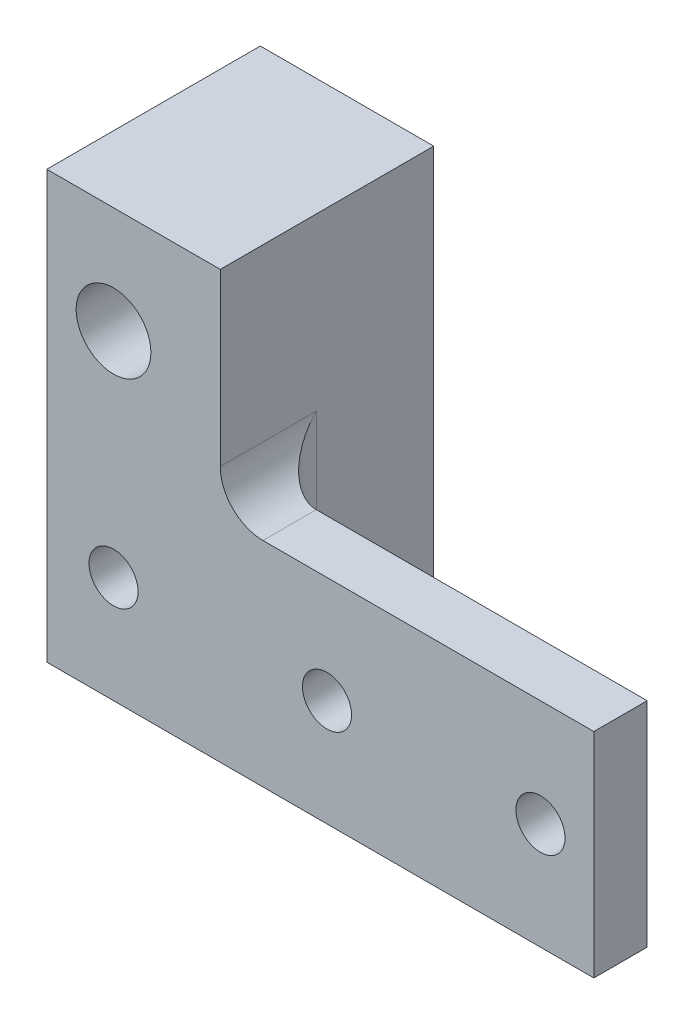
SolidWorks part; units mm, degrees
ref_plane "Front Plane" through (0, 0, 0) normal (0, 0, 1) x (1, 0, 0)
ref_plane "Top Plane" through (0, 0, 0) normal (0, 1, 0) x (1, 0, 0)
ref_plane "Right Plane" through (0, 0, 0) normal (1, 0, 0) x (0, 0, -1)
sketch "Sketch1" plane through (0, 0, 0) normal (0, 0, 1) x (1, 0, 0)
  line L0 (0, 0) -> (0, 50.8)
  line L1 (0, 50.8) -> (25.4, 50.8)
  line L2 (25.4, 50.8) -> (25.4, 25.4)
  line L3 (25.4, 25.4) -> (69.85, 25.4)
  line L4 (69.85, 25.4) -> (69.85, 0)
  line L5 (69.85, 0) -> (0, 0)
  dimension "D1" = 50.8
  dimension "D2" = 25.4
  dimension "2.75" = 69.85
extrude "Boss-Extrude1" add sketch "Sketch1" along normal blind 25.4
sketch "Sketch2" plane through (0, 0, 25.4) normal (0, 0, 1) x (1, 0, 0)
  line L0 (25.4, 50.8) -> (0, 50.8) construction
  line L1 (25.4, 25.4) -> (25.4, 50.8) construction
  line L2 (0, 0) -> (69.85, 0) construction
  circle A0 centre (12.7, 38.1) radius 2.921
  circle A1 centre (12.7, 12.7) radius 2.921
  circle A2 centre (38.1, 12.7) radius 2.921
  circle A3 centre (63.5, 12.7) radius 2.921
  dimension "D1" = 5.842
  dimension "D2" = 12.7
  dimension "D3" = 12.7
  dimension "D4" = 12.7
  dimension "D5" = 3
extrude "Cut-Extrude1" cut sketch "Sketch2" against normal through all
sketch "Sketch3" plane through (0, 0, 25.4) normal (0, 0, 1) x (1, 0, 0)
  line L0 (25.4, 50.8) -> (0, 50.8) construction
  line L1 (0, 0) -> (4.7625, 0)
  line L2 (0, 0) -> (0, 50.8)
  line L3 (0, 50.8) -> (4.7625, 50.8)
  line L4 (4.7625, 0) -> (4.7625, 50.8)
  dimension "D1" = 4.7625
extrude "Cut-Extrude2" cut sketch "Sketch3" against normal through all
sketch "Sketch4" plane through (0, 0, 0) normal (0, -1, 0) x (1, 0, 0)
  line L1 (69.85, 0) -> (25.4, 0)
  line L2 (69.85, 0) -> (69.85, 19.05)
  line L3 (69.85, 19.05) -> (25.4, 19.05)
  line L4 (25.4, 0) -> (25.4, 19.05)
  dimension "D1" = 19.05
  dimension "D2" = 44.45
extrude "Cut-Extrude3" cut sketch "Sketch4" against normal through all
fillet "Fillet1" radius 5.08 2 edges at (25.4, 12.7, 19.05) (25.4, 25.4, 22.225)
sketch "Sketch6" plane through (0, 0, 25.4) normal (0, 0, 1) x (1, 0, 0)
  circle A0 centre (12.7, 38.1) radius 4.445
  dimension "D1" = 8.89
extrude "Cut-Extrude5" cut sketch "Sketch6" against normal blind 12.7
